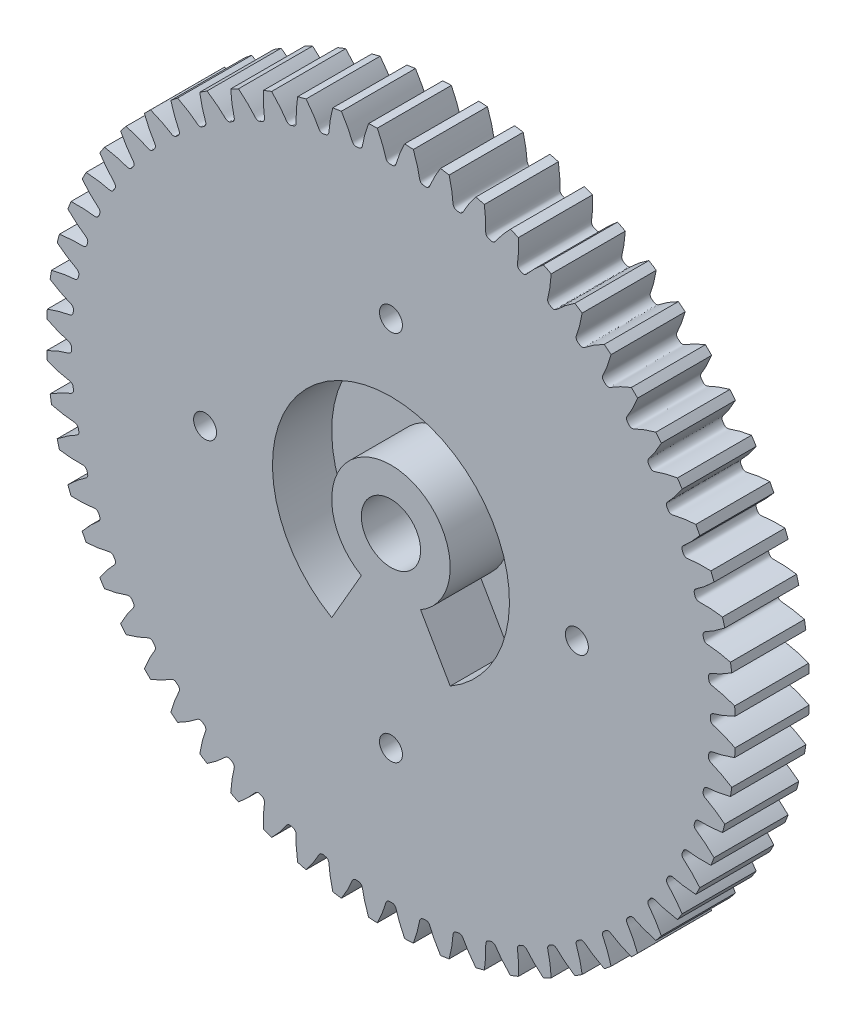
SolidWorks part; units mm, degrees
ref_plane "Front Plane" through (0, 0, 0) normal (0, 0, 1) x (1, 0, 0)
ref_plane "Top Plane" through (0, 0, 0) normal (0, 1, 0) x (1, 0, 0)
ref_plane "Right Plane" through (0, 0, 0) normal (1, 0, 0) x (0, 0, -1)
ref_axis "Axis1" through (0, 0, 5.5) along (0, 0, -1)
sketch "SketchRevolveSpurAssembly01Gear" plane through (0, 0, 0) normal (1, 0, 0) x (0, 0, -1)
  line L0 (0, 0) -> (1, 0) construction
  line L1 (-5, 0) -> (-5, 46.5)
  line L2 (-5, 46.5) -> (5, 46.5)
  line L3 (5, 46.5) -> (5, 0)
  line L4 (5, 0) -> (-5, 0)
  dimension "Side1" = 5
  dimension "OutsideRadius" = 46.5
  dimension "Side2" = 5
revolve "SpurAssembly01Gear" add sketch "SketchRevolveSpurAssembly01Gear" angle 360 about L0
sketch "SketchToothSpurAssembly01Gear" plane through (0, 0, 0) normal (0, 0, 1) x (1, 0, 0)
  arc A0 (46.5369, 1.8824) -> (46.5369, -1.8824) centre (0, 0) cw
  spline S0 degree 3 poles (46.5369, -1.8824) (46.4106, -1.8178) (46.2223, -1.724) (45.9725, -1.6049) (45.7913, -1.5209) (45.614, -1.4411) (45.4406, -1.3655) (45.2713, -1.2938) (45.1061, -1.2261) (44.945, -1.1621) (44.7882, -1.1018) (44.6356, -1.0452) (44.4874, -0.992) (44.3436, -0.9422) (44.2043, -0.8957) (44.0695, -0.8523) (43.9392, -0.8123) (43.7554, -0.7565) (43.5912, -0.7185) (43.4569, -0.6604) (43.397, -0.6284) (43.3333, -0.5856) (43.2647, -0.5249) (43.195, -0.4361) (43.14, -0.3154) (43.1191, -0.1635) (43.1282, 0) (43.1191, 0.1635) (43.14, 0.3154) (43.195, 0.4361) (43.2647, 0.5249) (43.3333, 0.5856) (43.397, 0.6284) (43.4569, 0.6604) (43.5912, 0.7185) (43.7554, 0.7565) (43.9392, 0.8123) (44.0695, 0.8523) (44.2043, 0.8957) (44.3436, 0.9422) (44.4874, 0.992) (44.6356, 1.0452) (44.7882, 1.1018) (44.945, 1.1621) (45.1061, 1.2261) (45.2713, 1.2938) (45.4406, 1.3655) (45.614, 1.4411) (45.7913, 1.5209) (45.9725, 1.6049) (46.2223, 1.724) (46.4106, 1.8178) (46.5369, 1.8824) knots 0 0 0 0 0.051766 0.076686 0.100963 0.124598 0.147592 0.169943 0.191651 0.212718 0.233143 0.252925 0.272065 0.290563 0.308419 0.325633 0.342204 0.358133 0.395729 0.403327 0.411415 0.420483 0.431261 0.444675 0.461387 0.478965 0.5 0.521035 0.538613 0.555325 0.568739 0.579517 0.588585 0.596673 0.604271 0.641867 0.657796 0.674367 0.691581 0.709437 0.727935 0.747075 0.766857 0.787282 0.808349 0.830057 0.852408 0.875402 0.899037 0.923314 0.948234 1 1 1 1
extrude "ToothExtrudeCutSpurAssembly01Gear" cut sketch "SketchToothSpurAssembly01Gear" against normal blind 5 and the other way blind 5
pattern_circular "PatternSpurAssembly01Gear" count 60 over 360 about axis through (0, 0, 5.5) along (0, 0, -1) of "ToothExtrudeCutSpurAssembly01Gear"
sketch "AuxiliarySketchSpurAssembly01Gear" plane through (0, 0, 0) normal (0, 0, 1) x (1, 0, 0)
  circle A0 centre (0, 0) radius 45 construction
  circle A1 centre (0, 0) radius 42.2862 construction
  circle A2 centre (0, 0) radius 43.6372 construction
  circle A3 centre (0, 0) radius 46.5 construction
  circle A4 centre (0, 0) radius 43.125 construction
  dimension "PitchDiameter" = 90
  dimension "BaseDiameter" = 84.5723
  dimension "FormDiameter" = 87.2745
  dimension "MajorDiameter" = 93
  dimension "MinorDiameter" = 86.25
sketch "Sketch3" plane through (0, 0, 5) normal (0, 0, 1) x (1, 0, 0)
  circle A0 centre (0, 0) radius 4
sketch "Sketch4" plane through (0, 0, 5) normal (0, 0, 1) x (1, 0, 0)
  line L0 (0, 0) -> (-9.5, -16.4545) construction
  line L1 (0, 0) -> (9.5, -16.4545) construction
  line L2 (-4, -6.9282) -> (-8, -13.8564)
  line L3 (4, -6.9282) -> (8, -13.8564)
  arc A1 (8, -13.8564) -> (-8, -13.8564) centre (0, 0) ccw
  arc A2 (4, -6.9282) -> (-4, -6.9282) centre (0, 0) ccw
sketch "Sketch5" plane through (0, 0, -5) normal (0, 0, -1) x (-1, 0, 0)
  circle A0 centre (0, 0) radius 4
extrude "Cut-Extrude2" cut sketch "Sketch5" against normal blind 18
sketch "Sketch6" plane through (0, 0, -5) normal (0, 0, -1) x (-1, 0, 0)
  circle A0 centre (25.1, 0) radius 1.55
extrude "Cut-Extrude3" cut sketch "Sketch6" against normal blind 10
pattern_circular "CirPattern2" count 4 over 360 about axis through (0, 0, 5.5) along (0, 0, -1) of "Cut-Extrude3"
extrude "Cut-Extrude4" cut sketch "Sketch4" against normal blind 8
sketch "Sketch7" plane through (0, 0, -5) normal (0, 0, -1) x (-1, 0, 0)
  circle A0 centre (-25.1, 0) radius 3
  circle A1 centre (0, 25.1) radius 3
  circle A2 centre (25.1, 0) radius 3
  circle A3 centre (0, -25.1) radius 3
  point P12 (0, 0)
  dimension "D1" = 4
extrude "Cut-Extrude5" cut sketch "Sketch7" against normal blind 3
